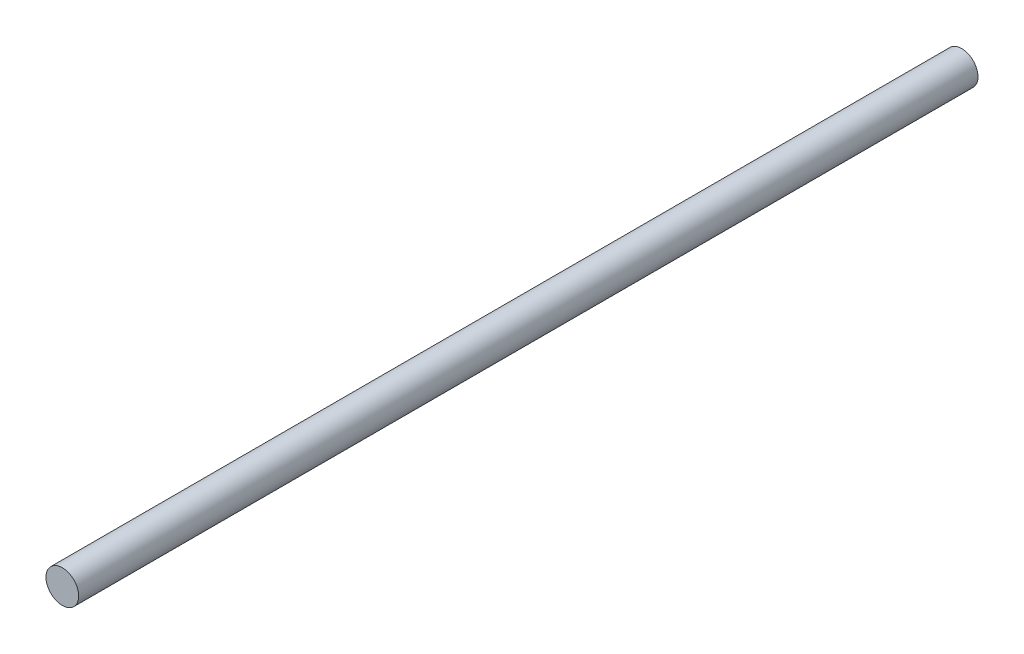
SolidWorks part; units mm, degrees
ref_plane "Front Plane" through (0, 0, 0) normal (0, 0, 1) x (1, 0, 0)
ref_plane "Top Plane" through (0, 0, 0) normal (0, 1, 0) x (1, 0, 0)
ref_plane "Right Plane" through (0, 0, 0) normal (1, 0, 0) x (0, 0, -1)
sketch "Sketch1" plane through (0, 0, 0) normal (0, 0, 1) x (1, 0, 0)
  circle A0 centre (0, 0) radius 4
  dimension "D1" = 8
extrude "Boss-Extrude1" add sketch "Sketch1" along normal blind 110 and the other way blind 110
